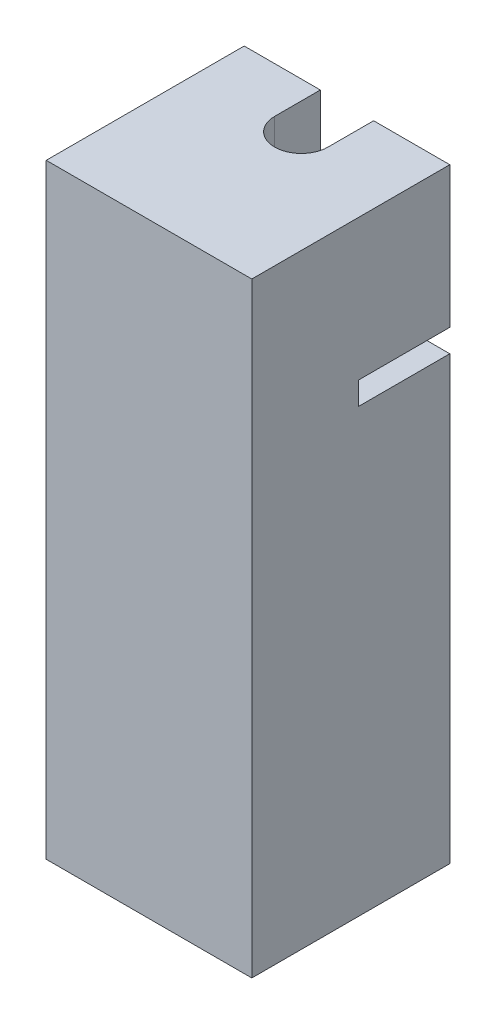
SolidWorks part; units mm, degrees
ref_plane "Front Plane" through (0, 0, 0) normal (0, 0, 1) x (1, 0, 0)
ref_plane "Top Plane" through (0, 0, 0) normal (0, 1, 0) x (1, 0, 0)
ref_plane "Right Plane" through (0, 0, 0) normal (1, 0, 0) x (0, 0, -1)
sketch "Sketch1" plane through (0, 0, 0) normal (0, 1, 0) x (1, 0, 0)
  line L0 (-6.75, 0) -> (6.75, 0) construction
  line L1 (-6.75, 3) -> (-1.75, 3)
  line L2 (-6.75, 3) -> (-6.75, -10)
  line L3 (-6.75, -10) -> (6.75, -10)
  line L4 (6.75, 3) -> (6.75, -10)
  line L5 (-1.75, 0) -> (-1.75, 3)
  line L6 (1.75, 0) -> (1.75, 3)
  line L7 (-1.75, 3) -> (1.75, 3) construction
  line L8 (1.75, 3) -> (6.75, 3)
  arc A0 (-1.75, 0) -> (1.75, 0) centre (0, 0) ccw
  arc A1 (1.75, 0) -> (-1.75, 0) centre (0, 0) ccw construction
  point P13 (0, 0)
  dimension "D1" = 3.5
  dimension "D2" = 5
  dimension "D3" = 3
  dimension "D4" = 10
extrude "Boss-Extrude1" add sketch "Sketch1" along normal mid plane 39.75
sketch "Sketch2" plane through (0, 0, -3) normal (0, 0, -1) x (-1, 0, 0)
  line L0 (6.75, 19.875) -> (6.75, -19.875) construction
  line L1 (-6.75, -19.875) -> (6.75, -19.875)
  line L2 (-6.75, -19.875) -> (-6.75, -10.625)
  line L3 (-6.75, -10.625) -> (6.75, -10.625)
  line L4 (6.75, -19.875) -> (6.75, -10.625)
  line L5 (-6.75, 19.875) -> (-6.75, -19.875) construction
  line L6 (-6.75, 9.125) -> (6.75, 9.125)
  line L7 (-6.75, 9.125) -> (-6.75, 10.625)
  line L8 (-6.75, 10.625) -> (6.75, 10.625)
  line L9 (6.75, 9.125) -> (6.75, 10.625)
  line L10 (-6.75, 10.625) -> (-6.75, 19.875) construction
  line M6 (-6.75, -19.875) -> (-1.75, -19.875)
  line M7 (-1.75, -19.875) -> (-1.75, 19.875)
  line M9 (-6.75, 19.875) -> (-6.75, -19.875)
  dimension "D1" = 1.5
  dimension "D2" = 19.75
extrude "Cut-Extrude1" cut sketch "Sketch2" against normal blind 6 contours L6 L9 L8 M7 | L8 L6 M9 M7 region at (4.25, 9.875, -3) region at (-2.5, 9.875, -3)
extrude "Boss-Extrude2" add sketch "Sketch2<3>" against normal through all contours L1 L4 L3 M7 | L3 M9 M6 M7 region at (4.25, -15.25, -3) region at (-2.5, -15.25, -3)
sketch "Sketch2<3>" plane through (0, 0, -3) normal (0, 0, -1) x (-1, 0, 0) same geometry as "Sketch2"
sketch "Sketch3" plane through (0, -10.625, 0) normal (0, 1, 0) x (1, 0, 0)
  line L3 (1.75, 0) -> (1.75, 3)
  line L4 (1.75, 3) -> (-1.75, 3)
  line L5 (-1.75, 3) -> (-1.75, 0)
  line L6 (1.75, 0) -> (1.75, 3)
  line L7 (1.75, 3) -> (-1.75, 3)
  line L8 (-1.75, 3) -> (-1.75, 0)
  arc A0 (1.75, 0) -> (-1.75, 0) centre (0, 0) ccw
  arc A1 (-1.75, 0) -> (1.75, 0) centre (0, 0) ccw construction
  arc A3 (-1.75, 0) -> (1.75, 0) centre (0, 0) ccw
  dimension "D1" = 0
extrude "Boss-Extrude3" add sketch "Sketch3" along normal blind 3
equation "\"length\"= 19.75mm"
equation "\"D1@Boss-Extrude1\"=\"length\"+20"
equation "\"D2@Sketch2\"=\"length\""
